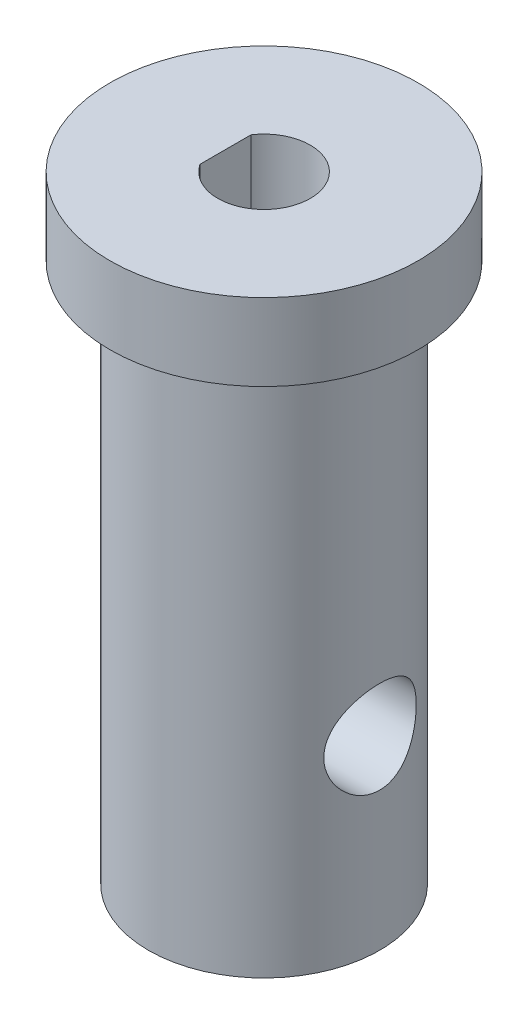
SolidWorks part; units mm, degrees
ref_plane "Front Plane" through (0, 0, 0) normal (0, 0, 1) x (1, 0, 0)
ref_plane "Top Plane" through (0, 0, 0) normal (0, 1, 0) x (1, 0, 0)
ref_plane "Right Plane" through (0, 0, 0) normal (1, 0, 0) x (0, 0, -1)
sketch "Sketch1" plane through (0, 0, 0) normal (0, 1, 0) x (1, 0, 0)
  circle A0 centre (0, 0) radius 10
  dimension "D1" = 20
extrude "MetalStock" add sketch "Sketch1" against normal blind 40 contours A0
sketch "Sketch2" plane through (0, 0, 0) normal (0, 1, 0) x (1, 0, 0)
  circle A1 centre (0, 0) radius 7.5
  dimension "D1" = 15
extrude "Cut-Extrude1" cut sketch "Sketch2" against normal up to surface (40 mm away) from offset 5 flip side to cut up to face at (0, -40, 10) offset against normal yes
sketch "Sketch6" plane through (0, 0, 0) normal (0, 1, 0) x (1, 0, 0)
  circle A1 centre (0, 0) radius 3
  dimension "D1" = 6
extrude "Cut-Extrude2" cut sketch "Sketch6" against normal blind 8
sketch "Sketch7" plane through (0, 0, 0) normal (0, 1, 0) x (1, 0, 0)
  line L1 (-4.5, 3) -> (-2.5, 3)
  line L2 (-4.5, 3) -> (-4.5, -3)
  line L3 (-4.5, -3) -> (-2.5, -3)
  line L4 (-2.5, 3) -> (-2.5, -3)
  line L5 (-4.5, 3) -> (-2.5, -3) construction
  line L6 (-4.5, -3) -> (-2.5, 3) construction
  circle A0 centre (0, 0) radius 3 construction
  circle A1 centre (0, 0) radius 3 construction
  point P0 (-3.5, 0)
  point P5 (0, 0)
  point P11 (-3.9534, 0)
  dimension "D1" = 2.5
  dimension "D2" = 2
extrude "Boss-Extrude1" add sketch "Sketch7" along normal up to surface from surface up to face at (0, 0, 3) starting at face at (0, -8, 3)
sketch "Sketch8" plane through (0, 0, 0) normal (1, 0, 0) x (0, 0, -1)
  line L0 (-7.5, -40) -> (7.5, -40) construction
  circle A3 centre (0, -28) radius 3
  point P3 (0, 0)
  dimension "D1" = 6
  dimension "D3" = 12
extrude "Cut-Extrude3" cut sketch "Sketch8" against normal through all both and the other way through all
